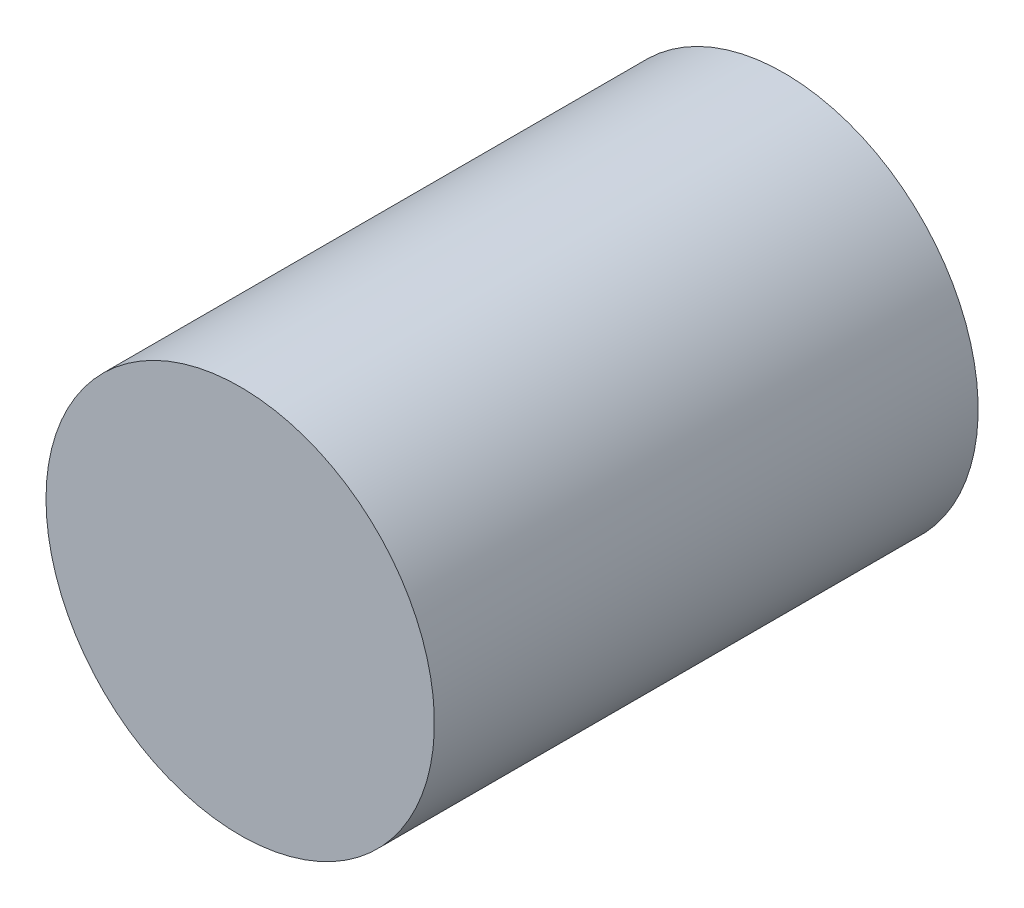
SolidWorks part; units mm, degrees
ref_plane "Front Plane" through (0, 0, 0) normal (0, 0, 1) x (1, 0, 0)
ref_plane "Top Plane" through (0, 0, 0) normal (0, 1, 0) x (1, 0, 0)
ref_plane "Right Plane" through (0, 0, 0) normal (1, 0, 0) x (0, 0, -1)
ref_plane "Plane1" through (0, 0, 2.5) normal (0, 0, -1) x (-1, 0, 0)
sketch "Sketch1" plane through (0, 0, 2.5) normal (0, 0, -1) x (-1, 0, 0)
  circle A0 centre (0, 92.5) radius 5
  dimension "D1" = 10
extrude "Boss-Extrude1" add sketch "Sketch1" along normal blind 7 and the other way blind 7
